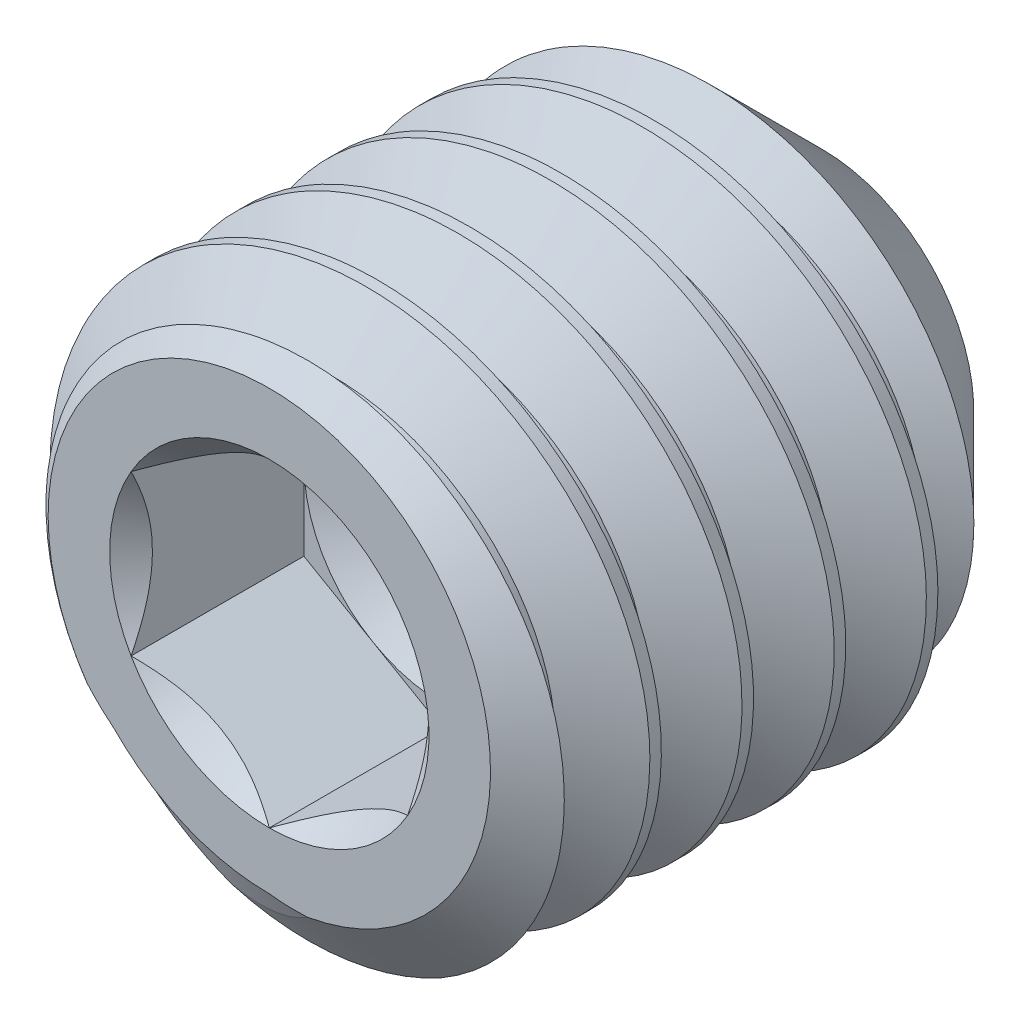
SolidWorks part; units mm, degrees
ref_plane "Front" through (0, 0, 0) normal (0, 0, 1) x (1, 0, 0)
ref_plane "Top" through (0, 0, 0) normal (0, 1, 0) x (1, 0, 0)
ref_plane "Right" through (0, 0, 0) normal (1, 0, 0) x (0, 0, -1)
sketch "Sketch22" plane through (0, 0, 0) normal (1, 0, 0) x (0, 0, -1)
  line L0 (-1.2531, 0) -> (-1.2531, 1.2)
  line L1 (-1.2531, 1.2) -> (-1.043, 1.5)
  line L2 (-1.043, 1.5) -> (1.0689, 1.5)
  line L3 (1.0689, 1.5) -> (1.7469, 0.8219)
  line L4 (1.7469, 0.8219) -> (1.2531, 0)
  line L5 (1.2531, 0) -> (-1.2531, 0)
  line L6 (1.2531, 0) -> (1.7469, 0) construction
  line L7 (1.7469, 0) -> (1.7469, 0.8219) construction
  line L8 (1.7469, -0.8219) -> (1.2531, 0) construction
  line L9 (-1.043, -1.5) -> (1.0689, -1.5) construction
  dimension "Dia" = 3
  dimension "Length" = 3
  dimension "D3" = 35
  dimension "D5" = 118
  dimension "D6" = 45
  dimension "D7" = 2.4
revolve "Revolve1" add sketch "Sketch22" angle 360 about L6
ref_plane "Plane1" through (0, 0, -1.7469) normal (0, 0, 1) x (1, 0, 0)
sketch "Sketch27" plane through (0, 0, -1.7469) normal (0, 0, 1) x (1, 0, 0)
  circle A0 centre (0, 0) radius 1.5 construction
  circle A1 centre (0, 0) radius 1.5
curve "Helix/Spiral1" pitch 0.5 height 3.5 turns 7
sketch "Sketch28" plane through (0, 0, 0) normal (1, 0, 0) x (0, 0, -1)
  line L0 (1.7469, 1.5) -> (2.1844, 1.5)
  line L1 (2.1844, 1.5) -> (1.9969, 1.1752)
  line L2 (1.9969, 1.1752) -> (1.9344, 1.1752)
  line L3 (1.9344, 1.1752) -> (1.7469, 1.5)
  line L4 (1.8407, 1.3376) -> (2.0907, 1.3376) construction
  line L6 (-1.043, 1.5) -> (1.0689, 1.5) construction
  dimension "D1" = 0.0625
  dimension "D3" = 60
  dimension "D2" = 0.25
sweep "Cut-Sweep2" cut profiles "Sketch28" path "Helix/Spiral1"
sketch "Sketch23" plane through (0, 0, 1.2531) normal (0, 0, 1) x (1, 0, 0)
  line L1 (0, 0.866) -> (-0.75, 0.433)
  line L2 (-0.75, 0.433) -> (-0.75, -0.433)
  line L3 (-0.75, -0.433) -> (0, -0.866)
  line L4 (0, -0.866) -> (0.75, -0.433)
  line L5 (0.75, -0.433) -> (0.75, 0.433)
  line L6 (0.75, 0.433) -> (0, 0.866)
  circle A0 centre (0, 0) radius 0.75 construction
  dimension "Hex" = 1.5
extrude "Cut-Extrude10" cut sketch "Sketch23" against normal blind 0.9375
sketch "Sketch24" plane through (0, 0, 1.2531) normal (0, 0, 1) x (1, 0, 0)
  circle A0 centre (0, 0) radius 0.866
extrude "Cut-Extrude11" cut sketch "Sketch24" against normal through all draft 45
sketch "Sketch26" plane through (0, 0, 0.3156) normal (0, 0, 1) x (1, 0, 0)
  circle A0 centre (0, 0) radius 0.75 construction
  circle A1 centre (0, 0) radius 0.75
extrude "Cut-Extrude12" cut sketch "Sketch26" against normal through all draft 60
sketch "Sketch30" plane through (0, 0, 0) normal (1, 0, 0) x (0, 0, -1)
  line L0 (-1.043, 1.5) -> (1.0689, 1.5) construction
  line L1 (-1.2531, 0) -> (-1.2531, 1.2) construction
  line L2 (1.7469, 0) -> (1.7469, 0.8219) construction
  line L3 (-1.043, -1.5) -> (1.0689, -1.5) construction
  point P0 (-1.2531, 1.5)
  point P1 (1.7469, 1.5)
  point P2 (1.7469, -1.5)
  point P11 (0.9969, -1.5)
  dimension "D1" = 0.75
sketch "Sketch31" plane through (0, 0, 0) normal (1, 0, 0) x (0, 0, -1)
  line L2 (1.2531, 0) -> (1.7469, -0.8219)
  line L3 (1.7469, 0.8219) -> (1.2531, 0)
equation "\"D7@Sketch22\"=\"Dia@Sketch22\"*.8"
equation "\"D1@Sketch28\" = \"D4@Helix/Spiral1\" * .125"
equation "\"D2@Sketch28\" = \"D4@Helix/Spiral1\" * .5"
equation "\"D3@Helix/Spiral1\" = \"Length@Sketch22\" + \"D4@Helix/Spiral1\""
equation "\"D1@Sketch30\" = \"D4@Helix/Spiral1\" * 1.5"
equation "\"hex Depth@Cut-Extrude10\" = \"Hex@Sketch23\" * .625"
